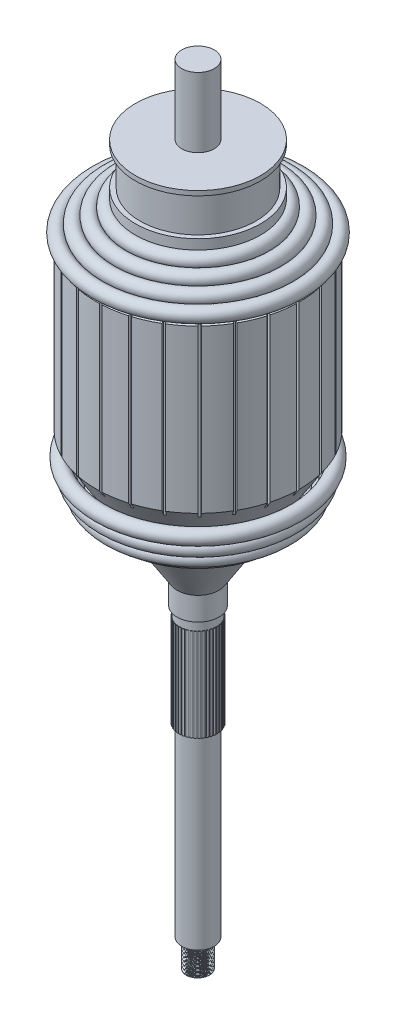
SolidWorks part; units mm, degrees
material "Copper"
ref_plane "Front Plane" through (0, 0, 0) normal (0, 0, 1) x (1, 0, 0)
ref_plane "Top Plane" through (0, 0, 0) normal (0, 1, 0) x (1, 0, 0)
ref_plane "Right Plane" through (0, 0, 0) normal (1, 0, 0) x (0, 0, -1)
sketch "Sketch1" plane through (0, 0, 0) normal (0, 0, 1) x (1, 0, 0)
  line L0 (0, 0) -> (0, 170) construction
  line L1 (0, 170) -> (3.5, 170)
  line L2 (3.5, 170) -> (3.5, 155)
  line L3 (3.5, 155) -> (13.5, 155)
  line L4 (13.5, 155) -> (13.5, 154)
  line L5 (13.5, 154) -> (12.5, 154)
  line L6 (12.5, 154) -> (12.5, 146)
  line L7 (12.5, 146) -> (13.5, 146)
  line L8 (13.5, 146) -> (13.5, 141)
  line L9 (13.5, 141) -> (21.9569, 135.6633)
  line L10 (21.9569, 135.6633) -> (21.9569, 100.6633)
  line L11 (21.9569, 100.6633) -> (4.5, 73)
  line L12 (4.5, 73) -> (4.5, 68)
  line L13 (2.5, 0) -> (0, 0)
  line L14 (0, 0) -> (0, 170)
  line L23 (4.5, 68) -> (4, 68)
  line L24 (4, 68) -> (4, 46)
  line L25 (4, 46) -> (3.5, 46)
  line L26 (3.5, 46) -> (3.5, 6)
  line L27 (3.5, 6) -> (2.5, 6)
  line L28 (2.5, 6) -> (2.5, 0)
  dimension "D1" = 170
  dimension "D2" = 3.5
  dimension "D3" = 15
  dimension "D4" = 10
  dimension "D5" = 1
  dimension "D6" = 1
  dimension "D7" = 8
  dimension "D8" = 1
  dimension "D9" = 5
  dimension "D10" = 10
  dimension "D11" = 35
  dimension "D12" = 5
  dimension "D13" = 0.5
  dimension "D14" = 22
  dimension "D15" = 0.5
  dimension "D16" = 40
  dimension "D17" = 1
  dimension "D18" = 6
  dimension "D19" = 2.5
revolve "Revolve1" add sketch "Sketch1" angle 360 about L14
ref_plane "Plane1" through (0, 180, 0) normal (0, -1, 0) x (-1, 0, 0)
sketch "Sketch2" plane through (0, 180, 0) normal (0, -1, 0) x (-1, 0, 0)
  line L0 (-20.518, 5.0871) -> (-21.3117, 5.2839)
  line L1 (-20.6335, 4.5962) -> (-21.4316, 4.774)
  line L2 (-18.8422, 9.5832) -> (-19.5711, 9.9539)
  line L3 (-18.6083, 10.0299) -> (-19.3281, 10.4179)
  line L4 (-15.867, 13.968) -> (-16.4808, 14.5083)
  line L5 (-15.5293, 14.3425) -> (-16.13, 14.8973)
  line L6 (-11.8948, 17.4751) -> (-12.3549, 18.1511)
  line L7 (-11.4746, 17.7539) -> (-11.9185, 18.4406)
  line L8 (-7.1753, 19.8843) -> (-7.4528, 20.6534)
  line L9 (-6.6989, 20.0497) -> (-6.958, 20.8253)
  line L10 (-2.0048, 21.044) -> (-2.0824, 21.8579)
  line L11 (-1.5023, 21.0858) -> (-1.5604, 21.9014)
  line L12 (3.2916, 20.8814) -> (3.4189, 21.6891)
  line L13 (3.7887, 20.797) -> (3.9353, 21.6014)
  line L14 (8.3812, 19.4068) -> (8.7054, 20.1574)
  line L15 (8.8417, 19.2014) -> (9.1837, 19.9441)
  line L16 (12.9441, 16.7128) -> (13.4448, 17.3592)
  line L17 (13.3391, 16.3993) -> (13.8551, 17.0336)
  line L18 (16.6938, 12.9686) -> (17.3395, 13.4703)
  line L19 (16.9984, 12.5668) -> (17.6559, 13.0528)
  line L20 (19.3945, 8.4096) -> (20.1446, 8.7349)
  line L21 (19.5896, 7.9446) -> (20.3473, 8.2519)
  line L22 (20.8766, 3.3222) -> (21.6841, 3.4507)
  line L23 (20.9499, 2.8233) -> (21.7602, 2.9325)
  line L24 (21.0469, -1.9739) -> (21.861, -2.0503)
  line L25 (20.9938, -2.4754) -> (21.8058, -2.5712)
  line L26 (19.8948, -7.1461) -> (20.6643, -7.4225)
  line L27 (19.7186, -7.6186) -> (20.4814, -7.9133)
  line L28 (17.4926, -11.8692) -> (18.1692, -12.3283)
  line L29 (17.2045, -12.2831) -> (17.8699, -12.7582)
  line L30 (13.9913, -15.8465) -> (14.5324, -16.4595)
  line L31 (13.6093, -16.1757) -> (14.1357, -16.8014)
  line L32 (9.6108, -18.8282) -> (9.9826, -19.5564)
  line L33 (9.159, -19.052) -> (9.5133, -19.789)
  line L34 (4.6265, -20.6268) -> (4.8055, -21.4246)
  line L35 (4.1332, -20.7312) -> (4.2931, -21.5331)
  line L36 (-0.6485, -21.1293) -> (-0.6736, -21.9466)
  line L37 (-1.1523, -21.1078) -> (-1.1969, -21.9243)
  line L38 (-5.8828, -20.3042) -> (-6.1103, -21.0896)
  line L39 (-6.3654, -20.1581) -> (-6.6116, -20.9378)
  line L40 (-10.7474, -18.2033) -> (-11.1631, -18.9074)
  line L41 (-11.1785, -17.9418) -> (-11.6109, -18.6358)
  line L42 (-14.9367, -14.9587) -> (-15.5145, -15.5373)
  line L43 (-15.2893, -14.5981) -> (-15.8807, -15.1628)
  line L44 (-18.1875, -10.7741) -> (-18.891, -11.1908)
  line L45 (-18.4394, -10.3372) -> (-19.1526, -10.7371)
  line L46 (-20.2956, -5.9126) -> (-21.0806, -6.1413)
  line L47 (-20.4308, -5.4268) -> (-21.2211, -5.6367)
  line L48 (-21.1283, -0.6795) -> (-21.9456, -0.7058)
  line L49 (-21.1385, -0.1753) -> (-21.9562, -0.1821)
  arc A0 (-21.3117, 5.2839) -> (-21.4316, 4.774) centre (0, 0) ccw
  arc A1 (-20.518, 5.0871) -> (-20.6335, 4.5962) centre (0, 0) ccw
  arc A2 (-18.6083, 10.0299) -> (-18.8422, 9.5832) centre (0, 0) ccw
  arc A3 (-19.3281, 10.4179) -> (-19.5711, 9.9539) centre (0, 0) ccw
  arc A4 (-15.5293, 14.3425) -> (-15.867, 13.968) centre (0, 0) ccw
  arc A5 (-16.13, 14.8973) -> (-16.4808, 14.5083) centre (0, 0) ccw
  arc A6 (-11.4746, 17.7539) -> (-11.8948, 17.4751) centre (0, 0) ccw
  arc A7 (-11.9185, 18.4406) -> (-12.3549, 18.1511) centre (0, 0) ccw
  arc A8 (-6.6989, 20.0497) -> (-7.1753, 19.8843) centre (0, 0) ccw
  arc A9 (-6.958, 20.8253) -> (-7.4528, 20.6534) centre (0, 0) ccw
  arc A10 (-1.5023, 21.0858) -> (-2.0048, 21.044) centre (0, 0) ccw
  arc A11 (-1.5604, 21.9014) -> (-2.0824, 21.8579) centre (0, 0) ccw
  arc A12 (3.7887, 20.797) -> (3.2916, 20.8814) centre (0, 0) ccw
  arc A13 (3.9353, 21.6014) -> (3.4189, 21.6891) centre (0, 0) ccw
  arc A14 (8.8417, 19.2014) -> (8.3812, 19.4068) centre (0, 0) ccw
  arc A15 (9.1837, 19.9441) -> (8.7054, 20.1574) centre (0, 0) ccw
  arc A16 (13.3391, 16.3993) -> (12.9441, 16.7128) centre (0, 0) ccw
  arc A17 (13.8551, 17.0336) -> (13.4448, 17.3592) centre (0, 0) ccw
  arc A18 (16.9984, 12.5668) -> (16.6938, 12.9686) centre (0, 0) ccw
  arc A19 (17.6559, 13.0528) -> (17.3395, 13.4703) centre (0, 0) ccw
  arc A20 (19.5896, 7.9446) -> (19.3945, 8.4096) centre (0, 0) ccw
  arc A21 (20.3473, 8.2519) -> (20.1446, 8.7349) centre (0, 0) ccw
  arc A22 (20.9499, 2.8233) -> (20.8766, 3.3222) centre (0, 0) ccw
  arc A23 (21.7602, 2.9325) -> (21.6841, 3.4507) centre (0, 0) ccw
  arc A24 (20.9938, -2.4754) -> (21.0469, -1.9739) centre (0, 0) ccw
  arc A25 (21.8058, -2.5712) -> (21.861, -2.0503) centre (0, 0) ccw
  arc A26 (19.7186, -7.6186) -> (19.8948, -7.1461) centre (0, 0) ccw
  arc A27 (20.4814, -7.9133) -> (20.6643, -7.4225) centre (0, 0) ccw
  arc A28 (17.2045, -12.2831) -> (17.4926, -11.8692) centre (0, 0) ccw
  arc A29 (17.8699, -12.7582) -> (18.1692, -12.3283) centre (0, 0) ccw
  arc A30 (13.6093, -16.1757) -> (13.9913, -15.8465) centre (0, 0) ccw
  arc A31 (14.1357, -16.8014) -> (14.5324, -16.4595) centre (0, 0) ccw
  arc A32 (9.159, -19.052) -> (9.6108, -18.8282) centre (0, 0) ccw
  arc A33 (9.5133, -19.789) -> (9.9826, -19.5564) centre (0, 0) ccw
  arc A34 (4.1332, -20.7312) -> (4.6265, -20.6268) centre (0, 0) ccw
  arc A35 (4.2931, -21.5331) -> (4.8055, -21.4246) centre (0, 0) ccw
  arc A36 (-1.1523, -21.1078) -> (-0.6485, -21.1293) centre (0, 0) ccw
  arc A37 (-1.1969, -21.9243) -> (-0.6736, -21.9466) centre (0, 0) ccw
  arc A38 (-6.3654, -20.1581) -> (-5.8828, -20.3042) centre (0, 0) ccw
  arc A39 (-6.6116, -20.9378) -> (-6.1103, -21.0896) centre (0, 0) ccw
  arc A40 (-11.1785, -17.9418) -> (-10.7474, -18.2033) centre (0, 0) ccw
  arc A41 (-11.6109, -18.6358) -> (-11.1631, -18.9074) centre (0, 0) ccw
  arc A42 (-15.2893, -14.5981) -> (-14.9367, -14.9587) centre (0, 0) ccw
  arc A43 (-15.8807, -15.1628) -> (-15.5145, -15.5373) centre (0, 0) ccw
  arc A44 (-18.4394, -10.3372) -> (-18.1875, -10.7741) centre (0, 0) ccw
  arc A45 (-19.1526, -10.7371) -> (-18.891, -11.1908) centre (0, 0) ccw
  arc A46 (-20.4308, -5.4268) -> (-20.2956, -5.9126) centre (0, 0) ccw
  arc A47 (-21.2211, -5.6367) -> (-21.0806, -6.1413) centre (0, 0) ccw
  arc A48 (-21.1385, -0.1753) -> (-21.1283, -0.6795) centre (0, 0) ccw
  arc A49 (-21.9562, -0.1821) -> (-21.9456, -0.7058) centre (0, 0) ccw
  point P104 (0, 0)
  dimension "D1" = 25
extrude "Cut-Extrude2" cut sketch "Sketch2" along normal blind 100
sketch "Sketch3" plane through (0, 46, 0) normal (0, -1, 0) x (1, 0, 0)
  line L0 (-0.0316, 3.9159) -> (0.1668, 3.8908)
  line L5 (-0.5218, 3.9658) -> (-0.3218, 3.9658)
  line L6 (-0.5218, 3.9658) -> (-0.5218, 3.8758)
  line L7 (-0.5218, 3.8758) -> (-0.3218, 3.8758)
  line L8 (-0.3218, 3.9658) -> (-0.3218, 3.8758)
  line L9 (0.1781, 3.9801) -> (0.1668, 3.8908)
  line L10 (-0.0204, 4.0051) -> (0.1781, 3.9801)
  line L11 (-0.0204, 4.0051) -> (-0.0316, 3.9159)
  line L12 (0.4597, 3.8941) -> (0.6534, 3.8444)
  line L13 (0.6758, 3.9316) -> (0.6534, 3.8444)
  line L14 (0.4821, 3.9813) -> (0.6758, 3.9316)
  line L15 (0.4821, 3.9813) -> (0.4597, 3.8941)
  line L16 (0.9445, 3.811) -> (1.1305, 3.7374)
  line L17 (1.1636, 3.8211) -> (1.1305, 3.7374)
  line L18 (0.9776, 3.8947) -> (1.1636, 3.8211)
  line L19 (0.9776, 3.8947) -> (0.9445, 3.811)
  line L20 (1.415, 3.6678) -> (1.5903, 3.5714)
  line L21 (1.6336, 3.6503) -> (1.5903, 3.5714)
  line L22 (1.4584, 3.7467) -> (1.6336, 3.6503)
  line L23 (1.4584, 3.7467) -> (1.415, 3.6678)
  line L24 (1.8639, 3.4667) -> (2.0257, 3.3492)
  line L25 (2.0786, 3.422) -> (2.0257, 3.3492)
  line L26 (1.9168, 3.5395) -> (2.0786, 3.422)
  line L27 (1.9168, 3.5395) -> (1.8639, 3.4667)
  line L28 (2.284, 3.211) -> (2.4298, 3.0741)
  line L29 (2.4914, 3.1397) -> (2.4298, 3.0741)
  line L30 (2.3456, 3.2766) -> (2.4914, 3.1397)
  line L31 (2.3456, 3.2766) -> (2.284, 3.211)
  line L32 (2.6688, 2.9046) -> (2.7963, 2.7505)
  line L33 (2.8656, 2.8079) -> (2.7963, 2.7505)
  line L34 (2.7381, 2.962) -> (2.8656, 2.8079)
  line L35 (2.7381, 2.962) -> (2.6688, 2.9046)
  line L36 (3.0121, 2.5524) -> (3.1193, 2.3835)
  line L37 (3.1953, 2.4318) -> (3.1193, 2.3835)
  line L38 (3.0881, 2.6006) -> (3.1953, 2.4318)
  line L39 (3.0881, 2.6006) -> (3.0121, 2.5524)
  line L40 (3.3086, 2.16) -> (3.3937, 1.979)
  line L41 (3.4752, 2.0173) -> (3.3937, 1.979)
  line L42 (3.39, 2.1983) -> (3.4752, 2.0173)
  line L43 (3.39, 2.1983) -> (3.3086, 2.16)
  line L44 (3.5535, 1.7335) -> (3.6153, 1.5433)
  line L45 (3.7009, 1.5711) -> (3.6153, 1.5433)
  line L46 (3.6391, 1.7613) -> (3.7009, 1.5711)
  line L47 (3.6391, 1.7613) -> (3.5535, 1.7335)
  line L48 (3.7431, 1.2796) -> (3.7806, 1.0832)
  line L49 (3.869, 1.1) -> (3.7806, 1.0832)
  line L50 (3.8315, 1.2965) -> (3.869, 1.1)
  line L51 (3.8315, 1.2965) -> (3.7431, 1.2796)
  line L52 (3.8743, 0.8056) -> (3.8868, 0.606)
  line L53 (3.9767, 0.6116) -> (3.8868, 0.606)
  line L54 (3.9641, 0.8112) -> (3.9767, 0.6116)
  line L55 (3.9641, 0.8112) -> (3.8743, 0.8056)
  line L56 (3.945, 0.3189) -> (3.9325, 0.1193)
  line L57 (4.0223, 0.1136) -> (3.9325, 0.1193)
  line L58 (4.0349, 0.3132) -> (4.0223, 0.1136)
  line L59 (4.0349, 0.3132) -> (3.945, 0.3189)
  line L60 (3.9542, -0.1729) -> (3.9167, -0.3693)
  line L61 (4.0051, -0.3862) -> (3.9167, -0.3693)
  line L62 (4.0426, -0.1898) -> (4.0051, -0.3862)
  line L63 (4.0426, -0.1898) -> (3.9542, -0.1729)
  line L64 (3.9017, -0.6619) -> (3.8399, -0.8521)
  line L65 (3.9255, -0.8799) -> (3.8399, -0.8521)
  line L66 (3.9873, -0.6897) -> (3.9255, -0.8799)
  line L67 (3.9873, -0.6897) -> (3.9017, -0.6619)
  line L68 (3.7883, -1.1405) -> (3.7031, -1.3215)
  line L69 (3.7846, -1.3598) -> (3.7031, -1.3215)
  line L70 (3.8697, -1.1788) -> (3.7846, -1.3598)
  line L71 (3.8697, -1.1788) -> (3.7883, -1.1405)
  line L72 (3.6158, -1.6011) -> (3.5086, -1.77)
  line L73 (3.5846, -1.8182) -> (3.5086, -1.77)
  line L74 (3.6918, -1.6493) -> (3.5846, -1.8182)
  line L75 (3.6918, -1.6493) -> (3.6158, -1.6011)
  line L76 (3.387, -2.0365) -> (3.2595, -2.1906)
  line L77 (3.3288, -2.2479) -> (3.2595, -2.1906)
  line L78 (3.4563, -2.0938) -> (3.3288, -2.2479)
  line L79 (3.4563, -2.0938) -> (3.387, -2.0365)
  line L80 (3.1053, -2.4397) -> (2.9595, -2.5766)
  line L81 (3.0211, -2.6422) -> (2.9595, -2.5766)
  line L82 (3.1669, -2.5053) -> (3.0211, -2.6422)
  line L83 (3.1669, -2.5053) -> (3.1053, -2.4397)
  line L84 (2.7754, -2.8045) -> (2.6136, -2.922)
  line L85 (2.6665, -2.9948) -> (2.6136, -2.922)
  line L86 (2.8283, -2.8773) -> (2.6665, -2.9948)
  line L87 (2.8283, -2.8773) -> (2.7754, -2.8045)
  line L88 (2.4023, -3.125) -> (2.2271, -3.2214)
  line L89 (2.2704, -3.3002) -> (2.2271, -3.2214)
  line L90 (2.4457, -3.2039) -> (2.2704, -3.3002)
  line L91 (2.4457, -3.2039) -> (2.4023, -3.125)
  line L92 (1.9921, -3.3963) -> (1.8061, -3.4699)
  line L93 (1.8392, -3.5536) -> (1.8061, -3.4699)
  line L94 (2.0252, -3.4799) -> (1.8392, -3.5536)
  line L95 (2.0252, -3.4799) -> (1.9921, -3.3963)
  line L96 (1.551, -3.614) -> (1.3573, -3.6637)
  line L97 (1.3797, -3.7509) -> (1.3573, -3.6637)
  line L98 (1.5734, -3.7011) -> (1.3797, -3.7509)
  line L99 (1.5734, -3.7011) -> (1.551, -3.614)
  line L100 (1.0862, -3.7746) -> (0.8877, -3.7997)
  line L101 (0.899, -3.889) -> (0.8877, -3.7997)
  line L102 (1.0974, -3.8639) -> (0.899, -3.889)
  line L103 (1.0974, -3.8639) -> (1.0862, -3.7746)
  line L104 (0.6048, -3.8758) -> (0.4048, -3.8758)
  line L105 (0.4048, -3.9658) -> (0.4048, -3.8758)
  line L106 (0.6048, -3.9658) -> (0.4048, -3.9658)
  line L107 (0.6048, -3.9658) -> (0.6048, -3.8758)
  line L108 (0.1146, -3.9159) -> (-0.0838, -3.8908)
  line L109 (-0.0951, -3.9801) -> (-0.0838, -3.8908)
  line L110 (0.1033, -4.0051) -> (-0.0951, -3.9801)
  line L111 (0.1033, -4.0051) -> (0.1146, -3.9159)
  line L112 (-0.3767, -3.8941) -> (-0.5705, -3.8444)
  line L113 (-0.5928, -3.9316) -> (-0.5705, -3.8444)
  line L114 (-0.3991, -3.9813) -> (-0.5928, -3.9316)
  line L115 (-0.3991, -3.9813) -> (-0.3767, -3.8941)
  line L116 (-0.8615, -3.811) -> (-1.0475, -3.7374)
  line L117 (-1.0806, -3.8211) -> (-1.0475, -3.7374)
  line L118 (-0.8946, -3.8947) -> (-1.0806, -3.8211)
  line L119 (-0.8946, -3.8947) -> (-0.8615, -3.811)
  line L120 (-1.332, -3.6678) -> (-1.5073, -3.5714)
  line L121 (-1.5506, -3.6503) -> (-1.5073, -3.5714)
  line L122 (-1.3754, -3.7467) -> (-1.5506, -3.6503)
  line L123 (-1.3754, -3.7467) -> (-1.332, -3.6678)
  line L124 (-1.7809, -3.4667) -> (-1.9427, -3.3492)
  line L125 (-1.9956, -3.422) -> (-1.9427, -3.3492)
  line L126 (-1.8338, -3.5395) -> (-1.9956, -3.422)
  line L127 (-1.8338, -3.5395) -> (-1.7809, -3.4667)
  line L128 (-2.201, -3.211) -> (-2.3468, -3.0741)
  line L129 (-2.4084, -3.1397) -> (-2.3468, -3.0741)
  line L130 (-2.2626, -3.2766) -> (-2.4084, -3.1397)
  line L131 (-2.2626, -3.2766) -> (-2.201, -3.211)
  line L132 (-2.5858, -2.9046) -> (-2.7133, -2.7505)
  line L133 (-2.7826, -2.8079) -> (-2.7133, -2.7505)
  line L134 (-2.6551, -2.962) -> (-2.7826, -2.8079)
  line L135 (-2.6551, -2.962) -> (-2.5858, -2.9046)
  line L136 (-2.9291, -2.5524) -> (-3.0363, -2.3835)
  line L137 (-3.1123, -2.4318) -> (-3.0363, -2.3835)
  line L138 (-3.0051, -2.6006) -> (-3.1123, -2.4318)
  line L139 (-3.0051, -2.6006) -> (-2.9291, -2.5524)
  line L140 (-3.2256, -2.16) -> (-3.3107, -1.979)
  line L141 (-3.3922, -2.0173) -> (-3.3107, -1.979)
  line L142 (-3.307, -2.1983) -> (-3.3922, -2.0173)
  line L143 (-3.307, -2.1983) -> (-3.2256, -2.16)
  line L144 (-3.4705, -1.7335) -> (-3.5323, -1.5433)
  line L145 (-3.6179, -1.5711) -> (-3.5323, -1.5433)
  line L146 (-3.5561, -1.7613) -> (-3.6179, -1.5711)
  line L147 (-3.5561, -1.7613) -> (-3.4705, -1.7335)
  line L148 (-3.6601, -1.2796) -> (-3.6976, -1.0832)
  line L149 (-3.786, -1.1) -> (-3.6976, -1.0832)
  line L150 (-3.7485, -1.2965) -> (-3.786, -1.1)
  line L151 (-3.7485, -1.2965) -> (-3.6601, -1.2796)
  line L152 (-3.7913, -0.8056) -> (-3.8039, -0.606)
  line L153 (-3.8937, -0.6116) -> (-3.8039, -0.606)
  line L154 (-3.8811, -0.8112) -> (-3.8937, -0.6116)
  line L155 (-3.8811, -0.8112) -> (-3.7913, -0.8056)
  line L156 (-3.862, -0.3189) -> (-3.8495, -0.1193)
  line L157 (-3.9393, -0.1136) -> (-3.8495, -0.1193)
  line L158 (-3.9519, -0.3132) -> (-3.9393, -0.1136)
  line L159 (-3.9519, -0.3132) -> (-3.862, -0.3189)
  line L160 (-3.8712, 0.1729) -> (-3.8337, 0.3693)
  line L161 (-3.9222, 0.3862) -> (-3.8337, 0.3693)
  line L162 (-3.9596, 0.1898) -> (-3.9222, 0.3862)
  line L163 (-3.9596, 0.1898) -> (-3.8712, 0.1729)
  line L164 (-3.8187, 0.6619) -> (-3.7569, 0.8521)
  line L165 (-3.8425, 0.8799) -> (-3.7569, 0.8521)
  line L166 (-3.9043, 0.6897) -> (-3.8425, 0.8799)
  line L167 (-3.9043, 0.6897) -> (-3.8187, 0.6619)
  line L168 (-3.7053, 1.1405) -> (-3.6201, 1.3215)
  line L169 (-3.7016, 1.3598) -> (-3.6201, 1.3215)
  line L170 (-3.7867, 1.1788) -> (-3.7016, 1.3598)
  line L171 (-3.7867, 1.1788) -> (-3.7053, 1.1405)
  line L172 (-3.5328, 1.6011) -> (-3.4256, 1.77)
  line L173 (-3.5016, 1.8182) -> (-3.4256, 1.77)
  line L174 (-3.6088, 1.6493) -> (-3.5016, 1.8182)
  line L175 (-3.6088, 1.6493) -> (-3.5328, 1.6011)
  line L176 (-3.304, 2.0365) -> (-3.1765, 2.1906)
  line L177 (-3.2458, 2.2479) -> (-3.1765, 2.1906)
  line L178 (-3.3733, 2.0938) -> (-3.2458, 2.2479)
  line L179 (-3.3733, 2.0938) -> (-3.304, 2.0365)
  line L180 (-3.0223, 2.4397) -> (-2.8765, 2.5766)
  line L181 (-2.9382, 2.6422) -> (-2.8765, 2.5766)
  line L182 (-3.0839, 2.5053) -> (-2.9382, 2.6422)
  line L183 (-3.0839, 2.5053) -> (-3.0223, 2.4397)
  line L184 (-2.6924, 2.8045) -> (-2.5306, 2.922)
  line L185 (-2.5835, 2.9948) -> (-2.5306, 2.922)
  line L186 (-2.7453, 2.8773) -> (-2.5835, 2.9948)
  line L187 (-2.7453, 2.8773) -> (-2.6924, 2.8045)
  line L188 (-2.3194, 3.125) -> (-2.1441, 3.2214)
  line L189 (-2.1874, 3.3002) -> (-2.1441, 3.2214)
  line L190 (-2.3627, 3.2039) -> (-2.1874, 3.3002)
  line L191 (-2.3627, 3.2039) -> (-2.3194, 3.125)
  line L192 (-1.9091, 3.3963) -> (-1.7231, 3.4699)
  line L193 (-1.7562, 3.5536) -> (-1.7231, 3.4699)
  line L194 (-1.9422, 3.4799) -> (-1.7562, 3.5536)
  line L195 (-1.9422, 3.4799) -> (-1.9091, 3.3963)
  line L196 (-1.468, 3.614) -> (-1.2743, 3.6637)
  line L197 (-1.2967, 3.7509) -> (-1.2743, 3.6637)
  line L198 (-1.4904, 3.7011) -> (-1.2967, 3.7509)
  line L199 (-1.4904, 3.7011) -> (-1.468, 3.614)
  line L200 (-1.0032, 3.7746) -> (-0.8047, 3.7997)
  line L201 (-0.816, 3.889) -> (-0.8047, 3.7997)
  line L202 (-1.0145, 3.8639) -> (-0.816, 3.889)
  line L203 (-1.0145, 3.8639) -> (-1.0032, 3.7746)
  circle A0 centre (0, 0) radius 4 construction
  point P205 (0.0415, 0)
  dimension "D1" = 0.2
  dimension "D2" = 0.09
  dimension "D3" = 50
extrude "Boss-Extrude1" add sketch "Sketch3" against normal blind 20
sketch "Sketch4" plane through (0, 46, 0) normal (0, -1, 0) x (1, 0, 0)
  line L0 (0.0907, 4.146) -> (0.4599, 4.089)
  line L1 (-0.5432, 3.9629) -> (-0.1696, 3.9629)
  line L2 (-0.5432, 3.9629) -> (-0.5432, 4.1113)
  line L3 (-0.5432, 4.1113) -> (-0.1696, 4.1113)
  line L4 (-0.1696, 3.9629) -> (-0.1696, 4.1113)
  line L5 (0.0681, 3.9994) -> (0.0907, 4.146)
  line L6 (0.0681, 3.9994) -> (0.4373, 3.9424)
  line L7 (0.4373, 3.9424) -> (0.4599, 4.089)
  line L8 (0.7225, 4.0836) -> (1.0787, 3.9709)
  line L9 (0.6778, 3.9422) -> (0.7225, 4.0836)
  line L10 (0.6778, 3.9422) -> (1.034, 3.8294)
  line L11 (1.034, 3.8294) -> (1.0787, 3.9709)
  line L12 (1.3374, 3.9254) -> (1.6722, 3.7597)
  line L13 (1.2716, 3.7925) -> (1.3374, 3.9254)
  line L14 (1.2716, 3.7925) -> (1.6064, 3.6267)
  line L15 (1.6064, 3.6267) -> (1.6722, 3.7597)
  line L16 (1.921, 3.6753) -> (2.2265, 3.4603)
  line L17 (1.8356, 3.5539) -> (1.921, 3.6753)
  line L18 (1.8356, 3.5539) -> (2.1412, 3.339)
  line L19 (2.1412, 3.339) -> (2.2265, 3.4603)
  line L20 (2.4595, 3.339) -> (2.7287, 3.0799)
  line L21 (2.3566, 3.2321) -> (2.4595, 3.339)
  line L22 (2.3566, 3.2321) -> (2.6258, 2.973)
  line L23 (2.6258, 2.973) -> (2.7287, 3.0799)
  line L24 (2.9404, 2.9244) -> (3.1668, 2.6273)
  line L25 (2.8224, 2.8345) -> (2.9404, 2.9244)
  line L26 (2.8224, 2.8345) -> (3.0489, 2.5374)
  line L27 (3.0489, 2.5374) -> (3.1668, 2.6273)
  line L28 (3.3523, 2.4413) -> (3.5308, 2.1131)
  line L29 (3.222, 2.3704) -> (3.3523, 2.4413)
  line L30 (3.222, 2.3704) -> (3.4004, 2.0422)
  line L31 (3.4004, 2.0422) -> (3.5308, 2.1131)
  line L32 (3.6857, 1.9009) -> (3.812, 1.5493)
  line L33 (3.5461, 1.8508) -> (3.6857, 1.9009)
  line L34 (3.5461, 1.8508) -> (3.6723, 1.4992)
  line L35 (3.6723, 1.4992) -> (3.812, 1.5493)
  line L36 (3.9327, 1.316) -> (4.0038, 0.9493)
  line L37 (3.787, 1.2878) -> (3.9327, 1.316)
  line L38 (3.787, 1.2878) -> (3.8582, 0.9211)
  line L39 (3.8582, 0.9211) -> (4.0038, 0.9493)
  line L40 (4.0875, 0.7003) -> (4.1018, 0.327)
  line L41 (3.9392, 0.6946) -> (4.0875, 0.7003)
  line L42 (3.9392, 0.6946) -> (3.9535, 0.3213)
  line L43 (3.9535, 0.3213) -> (4.1018, 0.327)
  line L44 (4.1465, 0.0682) -> (4.1036, -0.303)
  line L45 (3.9991, 0.0852) -> (4.1465, 0.0682)
  line L46 (3.9991, 0.0852) -> (3.9562, -0.286)
  line L47 (3.9562, -0.286) -> (4.1036, -0.303)
  line L48 (4.1083, -0.5656) -> (4.0093, -0.9258)
  line L49 (3.9652, -0.5263) -> (4.1083, -0.5656)
  line L50 (3.9652, -0.5263) -> (3.8662, -0.8865)
  line L51 (3.8662, -0.8865) -> (4.0093, -0.9258)
  line L52 (3.9738, -1.1861) -> (3.821, -1.527)
  line L53 (3.8384, -1.1254) -> (3.9738, -1.1861)
  line L54 (3.8384, -1.1254) -> (3.6856, -1.4663)
  line L55 (3.6856, -1.4663) -> (3.821, -1.527)
  line L56 (3.7462, -1.7788) -> (3.5431, -2.0924)
  line L57 (3.6216, -1.6982) -> (3.7462, -1.7788)
  line L58 (3.6216, -1.6982) -> (3.4186, -2.0117)
  line L59 (3.4186, -2.0117) -> (3.5431, -2.0924)
  line L60 (3.4307, -2.3298) -> (3.1822, -2.6087)
  line L61 (3.32, -2.2311) -> (3.4307, -2.3298)
  line L62 (3.32, -2.2311) -> (3.0714, -2.51)
  line L63 (3.0714, -2.51) -> (3.1822, -2.6087)
  line L64 (3.0349, -2.8262) -> (2.7467, -3.0639)
  line L65 (2.9405, -2.7117) -> (3.0349, -2.8262)
  line L66 (2.9405, -2.7117) -> (2.6523, -2.9494)
  line L67 (2.6523, -2.9494) -> (2.7467, -3.0639)
  line L68 (2.5679, -3.2563) -> (2.2468, -3.4472)
  line L69 (2.4921, -3.1288) -> (2.5679, -3.2563)
  line L70 (2.4921, -3.1288) -> (2.171, -3.3197)
  line L71 (2.171, -3.3197) -> (2.2468, -3.4472)
  line L72 (2.0407, -3.6102) -> (1.6942, -3.7498)
  line L73 (1.9853, -3.4726) -> (2.0407, -3.6102)
  line L74 (1.9853, -3.4726) -> (1.6388, -3.6122)
  line L75 (1.6388, -3.6122) -> (1.6942, -3.7498)
  line L76 (1.4657, -3.8794) -> (1.102, -3.9645)
  line L77 (1.4319, -3.7349) -> (1.4657, -3.8794)
  line L78 (1.4319, -3.7349) -> (1.0682, -3.82)
  line L79 (1.0682, -3.82) -> (1.102, -3.9645)
  line L80 (0.8564, -4.0576) -> (0.4839, -4.0862)
  line L81 (0.845, -3.9097) -> (0.8564, -4.0576)
  line L82 (0.845, -3.9097) -> (0.4725, -3.9383)
  line L83 (0.4725, -3.9383) -> (0.4839, -4.0862)
  line L84 (0.2269, -4.1408) -> (-0.1456, -4.1122)
  line L85 (0.2383, -3.9929) -> (0.2269, -4.1408)
  line L86 (0.2383, -3.9929) -> (-0.1342, -3.9643)
  line L87 (-0.1342, -3.9643) -> (-0.1456, -4.1122)
  line L88 (-0.4078, -4.1269) -> (-0.7716, -4.0418)
  line L89 (-0.374, -3.9825) -> (-0.4078, -4.1269)
  line L90 (-0.374, -3.9825) -> (-0.7378, -3.8974)
  line L91 (-0.7378, -3.8974) -> (-0.7716, -4.0418)
  line L92 (-1.033, -4.0163) -> (-1.3795, -3.8766)
  line L93 (-0.9776, -3.8787) -> (-1.033, -4.0163)
  line L94 (-0.9776, -3.8787) -> (-1.3241, -3.7391)
  line L95 (-1.3241, -3.7391) -> (-1.3795, -3.8766)
  line L96 (-1.634, -3.8115) -> (-1.9551, -3.6206)
  line L97 (-1.5582, -3.684) -> (-1.634, -3.8115)
  line L98 (-1.5582, -3.684) -> (-1.8793, -3.4931)
  line L99 (-1.8793, -3.4931) -> (-1.9551, -3.6206)
  line L100 (-2.1967, -3.5174) -> (-2.4849, -3.2798)
  line L101 (-2.1023, -3.403) -> (-2.1967, -3.5174)
  line L102 (-2.1023, -3.403) -> (-2.3905, -3.1653)
  line L103 (-2.3905, -3.1653) -> (-2.4849, -3.2798)
  line L104 (-2.7079, -3.1409) -> (-2.9564, -2.862)
  line L105 (-2.5971, -3.0422) -> (-2.7079, -3.1409)
  line L106 (-2.5971, -3.0422) -> (-2.8457, -2.7633)
  line L107 (-2.8457, -2.7633) -> (-2.9564, -2.862)
  line L108 (-3.1556, -2.6907) -> (-3.3587, -2.3772)
  line L109 (-3.0311, -2.6101) -> (-3.1556, -2.6907)
  line L110 (-3.0311, -2.6101) -> (-3.2341, -2.2965)
  line L111 (-3.2341, -2.2965) -> (-3.3587, -2.3772)
  line L112 (-3.5293, -2.1775) -> (-3.6822, -1.8366)
  line L113 (-3.394, -2.1168) -> (-3.5293, -2.1775)
  line L114 (-3.394, -2.1168) -> (-3.5468, -1.7759)
  line L115 (-3.5468, -1.7759) -> (-3.6822, -1.8366)
  line L116 (-3.8204, -1.6132) -> (-3.9194, -1.253)
  line L117 (-3.6773, -1.5739) -> (-3.8204, -1.6132)
  line L118 (-3.6773, -1.5739) -> (-3.7763, -1.2137)
  line L119 (-3.7763, -1.2137) -> (-3.9194, -1.253)
  line L120 (-4.0219, -1.0111) -> (-4.0647, -0.64)
  line L121 (-3.8745, -0.9941) -> (-4.0219, -1.0111)
  line L122 (-3.8745, -0.9941) -> (-3.9173, -0.623)
  line L123 (-3.9173, -0.623) -> (-4.0647, -0.64)
  line L124 (-4.1291, -0.3854) -> (-4.1148, -0.012)
  line L125 (-3.9808, -0.391) -> (-4.1291, -0.3854)
  line L126 (-3.9808, -0.391) -> (-3.9665, -0.0177)
  line L127 (-3.9665, -0.0177) -> (-4.1148, -0.012)
  line L128 (-4.1395, 0.2495) -> (-4.0684, 0.6162)
  line L129 (-3.9939, 0.2212) -> (-4.1395, 0.2495)
  line L130 (-3.9939, 0.2212) -> (-3.9228, 0.588)
  line L131 (-3.9228, 0.588) -> (-4.0684, 0.6162)
  line L132 (-4.0529, 0.8784) -> (-3.9266, 1.23)
  line L133 (-3.9133, 0.8283) -> (-4.0529, 0.8784)
  line L134 (-3.9133, 0.8283) -> (-3.787, 1.1799)
  line L135 (-3.787, 1.1799) -> (-3.9266, 1.23)
  line L136 (-3.8713, 1.4868) -> (-3.6929, 1.815)
  line L137 (-3.741, 1.4159) -> (-3.8713, 1.4868)
  line L138 (-3.741, 1.4159) -> (-3.5625, 1.7441)
  line L139 (-3.5625, 1.7441) -> (-3.6929, 1.815)
  line L140 (-3.599, 2.0603) -> (-3.3725, 2.3574)
  line L141 (-3.481, 1.9704) -> (-3.599, 2.0603)
  line L142 (-3.481, 1.9704) -> (-3.2545, 2.2675)
  line L143 (-3.2545, 2.2675) -> (-3.3725, 2.3574)
  line L144 (-3.2423, 2.5856) -> (-2.9731, 2.8446)
  line L145 (-3.1394, 2.4787) -> (-3.2423, 2.5856)
  line L146 (-3.1394, 2.4787) -> (-2.8703, 2.7377)
  line L147 (-2.8703, 2.7377) -> (-2.9731, 2.8446)
  line L148 (-2.8096, 3.0502) -> (-2.5041, 3.2651)
  line L149 (-2.7243, 2.9289) -> (-2.8096, 3.0502)
  line L150 (-2.7243, 2.9289) -> (-2.4187, 3.1438)
  line L151 (-2.4187, 3.1438) -> (-2.5041, 3.2651)
  line L152 (-2.3111, 3.4434) -> (-1.9763, 3.6091)
  line L153 (-2.2453, 3.3104) -> (-2.3111, 3.4434)
  line L154 (-2.2453, 3.3104) -> (-1.9105, 3.4762)
  line L155 (-1.9105, 3.4762) -> (-1.9763, 3.6091)
  line L156 (-1.7584, 3.7558) -> (-1.4022, 3.8685)
  line L157 (-1.7136, 3.6143) -> (-1.7584, 3.7558)
  line L158 (-1.7136, 3.6143) -> (-1.3574, 3.7271)
  line L159 (-1.3574, 3.7271) -> (-1.4022, 3.8685)
  line L160 (-1.1645, 3.9802) -> (-0.7952, 4.0372)
  line L161 (-1.1418, 3.8336) -> (-1.1645, 3.9802)
  line L162 (-1.1418, 3.8336) -> (-0.7726, 3.8906)
  line L163 (-0.7726, 3.8906) -> (-0.7952, 4.0372)
  arc A0 (-0.021, 3.9999) -> (-0.4073, -3.9792) centre (0, 0) ccw construction
  point P169 (0, 0)
  dimension "D1" = 41
extrude "Boss-Extrude2" add sketch "Sketch4" against normal blind 20
thread "Thread1" pitch 0.25 method cut profile "Thread Profile1" start angle 0, offset 0, length 0, pitch 0.25, diameter 5
ref_plane "Plane2" through (-2.5, 6, 0) normal (0, 0, 1) x (-1, 0, 0)
sketch "Thread Profile1" plane through (-2.5, 6, 0) normal (0, 0, 1) x (-1, 0, 0)
  line L0 (0, 0) -> (0, 0.25) construction
  line L11 (0, 0) -> (0, 0.2187)
  line L12 (0, 0.2187) -> (-0.1353, 0.1406)
  line L13 (-0.1353, 0.1406) -> (-0.1353, 0.0781)
  line L15 (-0.1353, 0.0781) -> (0, 0)
  line L17 (-0.1353, 0.1094) -> (0, 0.1094) construction
  point P2 (0, 0)
  dimension "Pitch" = 0.25
  dimension "Profile_Angle" = 60
  dimension "Profile_Land" = 0.0625
  dimension "Profile_Height" = 0.1353
sketch "Sketch5" plane through (0, 0, 0) normal (1, 0, 0) x (0, 0, -1)
  line L0 (21.9569, 135.6633) -> (13.5, 141) construction
  line L1 (21.8579, 135.6633) -> (20.8253, 135.6633) construction
  circle A0 centre (21.5983, 137.6633) radius 1.5
  circle A1 centre (19.0612, 139.2643) radius 1.5
  circle A2 centre (16.5242, 140.8653) radius 1.5
  circle A3 centre (13.9871, 142.4663) radius 1.5
  circle A4 centre (21.1068, 95.7429) radius 1.5
  circle A5 centre (20.0513, 92.9347) radius 1.5
  circle A6 centre (18.8137, 90.2019) radius 1.5
  circle A7 centre (16.4804, 88.3163) radius 1.5
  point P20 (15.661, 89.5684)
  point P21 (0, 0)
  point P22 (21.5983, 96.43)
  point P23 (16.5242, 88.3743)
  point P24 (18.2868, 90.7115)
  point P25 (20.0513, 92.9347)
  dimension "D1" = 3
  dimension "D6" = 3
  dimension "D2" = 3
  dimension "D3" = 2
  dimension "D4" = 3
  dimension "D5" = 3
  dimension "D7" = 3
  dimension "D8" = 3
  dimension "D9" = 3
revolve "Revolve2" add sketch "Sketch5" angle 360 about axis through (0, 0, 0) along (0, -1, 0)
